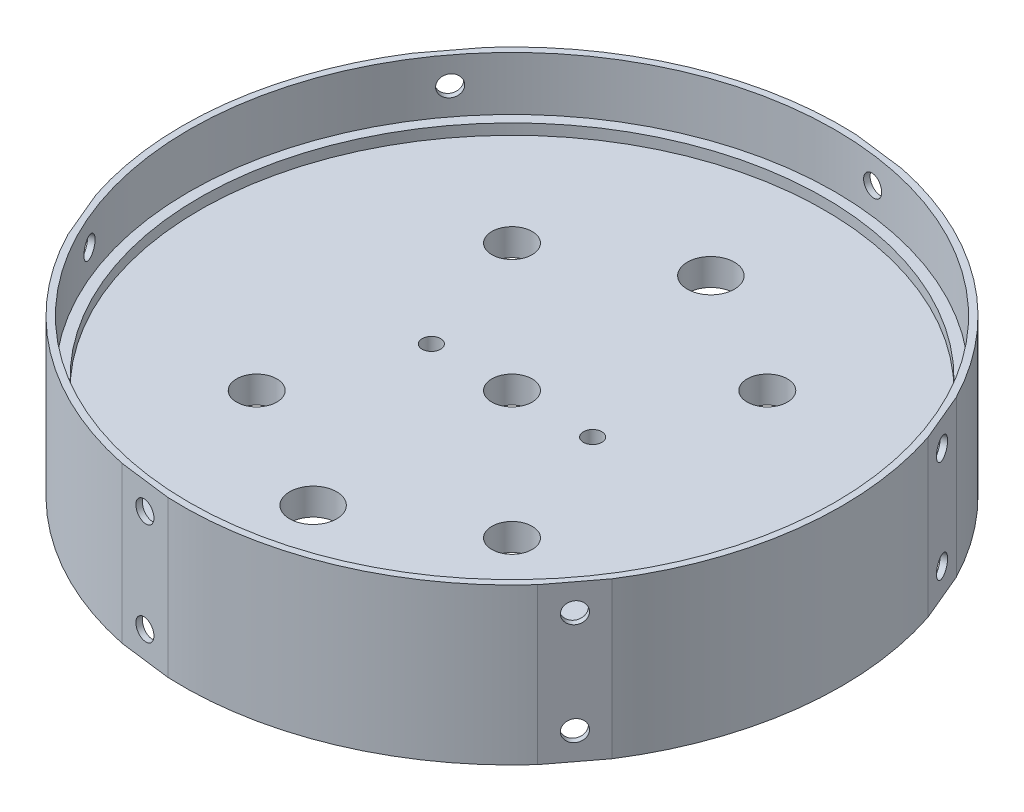
SolidWorks part; units mm, degrees
material "6061-T6 (SS)"
ref_plane "Front Plane" through (0, 0, 0) normal (0, 0, 1) x (1, 0, 0)
ref_plane "Top Plane" through (0, 0, 0) normal (0, 1, 0) x (1, 0, 0)
ref_plane "Right Plane" through (0, 0, 0) normal (1, 0, 0) x (0, 0, -1)
ref_axis "Axis1" through (0, 55, 0) along (0, -1, 0)
sketch "Sketch3" plane through (0, 0, 0) normal (0, 1, 0) x (1, 0, 0)
  circle A0 centre (0, 0) radius 77.8637
  dimension "D1" = 155.7274
extrude "Boss-Extrude1" add sketch "Sketch3" along normal blind 3.175 and the other way blind 3.175
sketch "Sketch4" plane through (0, 3.175, 0) normal (0, 1, 0) x (1, 0, 0)
  circle A0 centre (0, 0) radius 77.8637
  circle A1 centre (0, 0) radius 73.8505
  dimension "D1" = 155.7274
  dimension "D2" = 147.701
extrude "Boss-Extrude3" add sketch "Sketch4" along normal blind 2.54
sketch "Sketch6" plane through (0, 5.715, 0) normal (0, 1, 0) x (1, 0, 0)
  circle A0 centre (0, 0) radius 77.8637
  circle A1 centre (0, 0) radius 76.2889
  dimension "D1" = 155.7274
  dimension "D2" = 152.5778
extrude "Boss-Extrude4" add sketch "Sketch6" along normal blind 12.7
hole_wizard "#10 (0.1935) Diameter Hole1" positions "3DSketch2" profile "Sketch7" hole size "#10" standard "ANSI Inch" end condition up to next
sketch3d "3DSketch2"
  point P0 (-9.7724, 12.065, 77.248)
  dimension "D1" = 6.35
sketch "Sketch7" plane through (-9.7724, 12.065, 77.248) normal (0, 1, 0) x (0.9921, 0, 0.1255)
  line L0 (0, 0) -> (0, 184.7583)
  line L1 (0, 184.7583) -> (2.4574, 184.7583)
  line L2 (2.4574, 184.7583) -> (2.4574, 0)
  line L5 (2.4574, 0) -> (0, 0)
  line L11 (0, -6.35) -> (0, 107.95) construction
  dimension "Thru Hole Dia." = 4.9149
  dimension "Thru Hole Depth" = 184.7583
pattern_circular "CirPattern2" count 6 over 360 about axis through (0, 55, 0) along (0, -1, 0) of "#10 (0.1935) Diameter Hole1"
mirror "Mirror3" about plane through (0, 0, 0) normal (0, 1, 0) of "Boss-Extrude3", "Boss-Extrude4", "#10 (0.1935) Diameter Hole1", "CirPattern2"
hole_wizard "3/8 (0.375) Diameter Hole1" positions "Sketch8" profile "Sketch9" hole size "3/8" standard "ANSI Inch" end condition up to next
sketch "Sketch8" plane through (0, 3.175, 0) normal (0, 1, 0) x (1, 0, 0)
  line L0 (-30.1625, 30.1625) -> (30.1625, -30.1625) construction
  point P0 (-30.1625, 30.1625)
  point P2 (30.1625, 30.1625)
  point P4 (30.1625, -30.1625)
  point P6 (-30.1625, -30.1625)
  point P17 (0, 0)
  dimension "D1" = 60.325
  dimension "D2" = 60.325
sketch "Sketch9" plane through (-30.1625, 3.175, -30.1625) normal (1, 0, 0) x (0, 0, 1)
  line L0 (0, 0) -> (0, 6.35)
  line L1 (0, 6.35) -> (4.7625, 6.35)
  line L2 (4.7625, 6.35) -> (4.7625, 0)
  line L5 (4.7625, 0) -> (0, 0)
  line L11 (0, -6.35) -> (0, 107.95) construction
  dimension "Thru Hole Dia." = 9.525
  dimension "Thru Hole Depth" = 6.35
ref_axis "Axis2" through (-9.556, 12.065, 75.5373) along (-0.1255, 0, 0.9921)
ref_plane "Plane1" through (-9.7724, 0, 77.248) normal (-0.1255, 0, 0.9921) x (0.9921, 0, 0.1255)
sketch "Sketch11" plane through (-9.7724, 0, 77.248) normal (-0.1255, 0, 0.9921) x (0.9921, 0, 0.1255)
  line L1 (-20.18, 23.5914) -> (21.0466, 23.5914)
  line L2 (-20.18, 23.5914) -> (-20.18, -28.7325)
  line L3 (-20.18, -28.7325) -> (21.0466, -28.7325)
  line L4 (21.0466, 23.5914) -> (21.0466, -28.7325)
extrude "Cut-Extrude2" cut sketch "Sketch11" against normal blind 0.254
pattern_circular "CirPattern4" count 6 over 360 about axis through (0, 55, 0) along (0, -1, 0) of "Cut-Extrude2"
hole_wizard "3/8 (0.375) Diameter Hole2" positions "Sketch12" profile "Sketch13" hole size "3/8" standard "ANSI Inch" end condition up to next
sketch "Sketch12" plane through (0, 3.175, 0) normal (0, 1, 0) x (1, 0, 0)
  point P0 (0, 0)
sketch "Sketch13" plane through (0, 3.175, 0) normal (1, 0, 0) x (0, 0, 1)
  line L0 (0, 0) -> (0, 6.35)
  line L1 (0, 6.35) -> (4.7625, 6.35)
  line L2 (4.7625, 6.35) -> (4.7625, 0)
  line L5 (4.7625, 0) -> (0, 0)
  line L11 (0, -6.35) -> (0, 107.95) construction
  dimension "Thru Hole Dia." = 9.525
  dimension "Thru Hole Depth" = 6.35
hole_wizard "7/16 (0.4375) Diameter Hole1" positions "Sketch14" profile "Sketch15" hole size "7/16" standard "ANSI Inch" end condition up to next
sketch "Sketch14" plane through (0, 3.175, 0) normal (0, 1, 0) x (1, 0, 0)
  line L2 (0, -11.8745) -> (0, 11.8745) construction
  line L3 (0, -46.99) -> (0, 46.99) construction
  point P0 (0, -46.99)
  point P2 (0, 46.99)
  point P29 (0, 0)
  dimension "D1" = 93.98
sketch "Sketch15" plane through (0, 3.175, 46.99) normal (1, 0, 0) x (0, 0, 1)
  line L0 (0, 0) -> (0, 6.35)
  line L1 (0, 6.35) -> (5.5562, 6.35)
  line L2 (5.5562, 6.35) -> (5.5562, 0)
  line L5 (5.5562, 0) -> (0, 0)
  line L11 (0, -6.35) -> (0, 107.95) construction
  dimension "Thru Hole Dia." = 11.1125
  dimension "Thru Hole Depth" = 6.35
hole_wizard "11/64 (0.17188) Diameter Hole1" positions "Sketch16" profile "Sketch17" hole size "11/64" standard "ANSI Inch" end condition up to next
sketch "Sketch16" plane through (0, 3.175, 0) normal (0, 1, 0) x (1, 0, 0)
  line L0 (19.05, 0) -> (-19.05, 0) construction
  point P0 (-19.05, 0)
  point P2 (19.05, 0)
  point P11 (0, 0)
  dimension "D1" = 38.1
sketch "Sketch17" plane through (-19.05, 3.175, 0) normal (1, 0, 0) x (0, 0, 1)
  line L0 (0, 0) -> (0, 6.35)
  line L1 (0, 6.35) -> (2.1829, 6.35)
  line L2 (2.1829, 6.35) -> (2.1829, 0)
  line L5 (2.1829, 0) -> (0, 0)
  line L11 (0, -6.35) -> (0, 107.95) construction
  dimension "Thru Hole Dia." = 4.3658
  dimension "Thru Hole Depth" = 6.35
